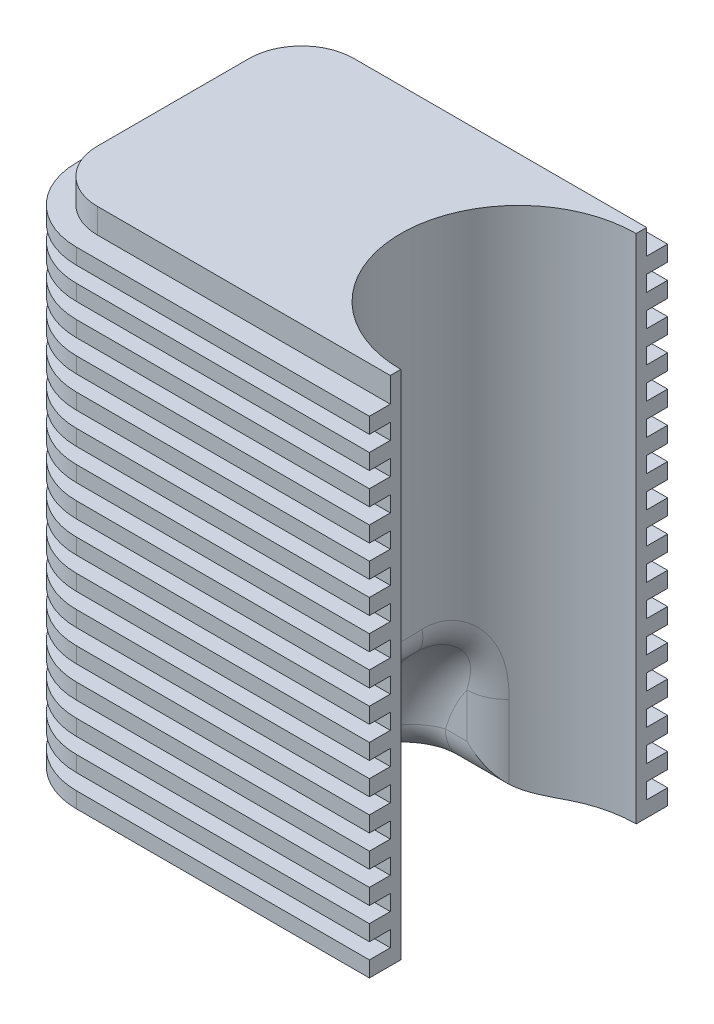
SolidWorks part; units mm, degrees
ref_plane "Ön Düzlem" through (0, 0, 0) normal (0, 0, 1) x (1, 0, 0)
ref_plane "Üst Düzlem" through (0, 0, 0) normal (0, 1, 0) x (1, 0, 0)
ref_plane "Sağ Düzlem" through (0, 0, 0) normal (1, 0, 0) x (0, 0, -1)
sketch "Sketch1" plane through (0, 0, 0) normal (0, 0, 1) x (1, 0, 0)
  line L0 (-32.985, 38.875) -> (-32.985, 48.875)
  line L1 (-22.985, 48.875) -> (32.985, 48.875)
  line L2 (-32.985, 38.875) -> (-32.985, -48.875)
  line L3 (-32.985, -48.875) -> (32.985, -48.875)
  line L4 (32.985, 48.875) -> (32.985, -48.875)
  line L5 (-32.985, 48.875) -> (32.985, -48.875) construction
  line L6 (-32.985, -48.875) -> (32.985, 48.875) construction
  line L7 (-32.985, 48.875) -> (-22.985, 48.875)
  point P0 (0, 0)
  dimension "D1" = 65.97
  dimension "D2" = 97.75
extrude "Boss-Extrude1" add sketch "Sketch1" along normal mid plane 49
sketch "Sketch2" plane through (0, 48.875, 0) normal (0, 1, 0) x (1, 0, 0)
  line L0 (32.985, -24.5) -> (32.985, 24.5) construction
  circle A0 centre (32.985, 0) radius 22.5
  dimension "D1" = 45
extrude "Cut-Extrude1" cut sketch "Sketch2" against normal up to surface (97.75 mm away) up to face at (0, -48.875, 0)
sketch "Sketch3" plane through (0, 0, 0) normal (0, 0, 1) x (1, 0, 0)
  circle A0 centre (32.985, -48.875) radius 35
  dimension "D1" = 70
extrude "Cut-Extrude2" cut sketch "Sketch3" against normal mid plane 25
fillet "Fillet1" radius 7.5 8 edges at (14.2767, -34.0848, -12.5) (6.1309, -48.875, -12.5) (-2.015, -48.875, 0) (2.3273, -31.9899, 12.5) (10.4911, -22.0604, -0.5234) (2.3273, -31.9899, -12.5) (6.1309, -48.875, 12.5) (14.2767, -34.0848, 12.5)
fillet "Fillet3" radius 10 2 edges at (-32.985, 0, -24.5) (-32.985, 0, 24.5)
sketch "Sketch7" plane through (0, -48.875, 0) normal (0, -1, 0) x (1, 0, 0)
  line L0 (32.985, 28.5) -> (-22.985, 28.5)
  line L1 (-36.985, 14.5) -> (-36.985, -14.5)
  line L2 (-22.985, -28.5) -> (32.985, -28.5)
  line L3 (32.985, 28.5) -> (32.985, 24.5)
  line L4 (32.985, -28.5) -> (32.985, -24.5)
  line L8 (-32.985, 14.5) -> (-32.985, -14.5)
  line L9 (-22.985, -24.5) -> (32.985, -24.5)
  line L10 (32.985, -24.5) -> (32.985, -22.5)
  line L11 (22.6772, -20) -> (6.5275, -20)
  line L12 (-8.848, -5) -> (-8.848, 5)
  line L13 (6.5275, 20) -> (22.6772, 20)
  line L14 (32.985, 22.5) -> (32.985, 24.5)
  line L15 (32.985, 24.5) -> (-22.985, 24.5)
  line L16 (-32.985, 14.5) -> (-32.985, -14.5)
  line L17 (-22.985, -24.5) -> (32.985, -24.5)
  line L18 (32.985, -24.5) -> (32.985, -22.5)
  line L22 (32.985, 22.5) -> (32.985, 24.5)
  line L23 (32.985, 24.5) -> (-22.985, 24.5)
  arc A0 (-22.985, 28.5) -> (-36.985, 14.5) centre (-22.985, 14.5) ccw
  arc A1 (-36.985, -14.5) -> (-22.985, -28.5) centre (-22.985, -14.5) ccw
  arc A4 (-32.985, -14.5) -> (-22.985, -24.5) centre (-22.985, -14.5) ccw
  arc A5 (22.6772, -20) -> (32.985, -22.5) centre (32.985, 0) ccw
  arc A6 (32.985, 22.5) -> (22.6772, 20) centre (32.985, 0) ccw
  arc A7 (-22.985, 24.5) -> (-32.985, 14.5) centre (-22.985, 14.5) ccw
  arc A8 (-32.985, -14.5) -> (-22.985, -24.5) centre (-22.985, -14.5) ccw
  arc A11 (-22.985, 24.5) -> (-32.985, 14.5) centre (-22.985, 14.5) ccw
  spline S2 degree 3 poles (320.5988, 929.3983) (147.1047, 209.6077) (54.4476, -29.3078) (3.0778, -19.6329) (2.5954, -19.5185) (1.6385, -19.2426) (1.1617, -19.0801) (-0.2292, -18.5296) (-1.1097, -18.0786) (-2.3606, -17.2767) (-2.7659, -16.9884) (-3.552, -16.3679) (-3.9294, -16.0382) (-5.0015, -15.0044) (-5.6426, -14.2512) (-6.4921, -13.0238) (-6.7578, -12.5957) (-7.2406, -11.7219) (-7.4584, -11.2759) (-8.0429, -9.9107) (-8.3412, -8.9649) (-19.9708, 47.4584) (290.1679, 138.7175) (991.1415, -8.1364) knots -6.415531 -6.415531 -6.415531 -6.415531 0.125 0.125 0.1875 0.1875 0.25 0.25 0.375 0.375 0.4375 0.4375 0.5 0.5 0.625 0.625 0.6875 0.6875 0.75 0.75 0.875 0.875 7.923707 7.923707 7.923707 7.923707 only from (6.5275, -20) to (-8.848, -5)
  spline S3 degree 3 poles (946.3703, -290.8944) (171.131, -113.2774) (-17.4982, -35.7953) (-8.4491, 8.4449) (-8.3255, 8.9256) (-8.0281, 9.8786) (-7.854, 10.3509) (-7.2679, 11.7231) (-6.7901, 12.5897) (-5.9438, 13.8176) (-5.6381, 14.217) (-4.9918, 14.9787) (-4.6519, 15.3409) (-3.5834, 16.373) (-2.8066, 16.989) (-1.1206, 18.0735) (-0.2353, 18.5262) (1.145, 19.074) (1.6142, 19.2348) (2.5714, 19.5124) (3.0609, 19.6293) (69.7275, 32.2412) (186.0404, -379.5955) (318.7265, -930.0151) knots -5.514491 -5.514491 -5.514491 -5.514491 0.125 0.125 0.1875 0.1875 0.25 0.25 0.375 0.375 0.4375 0.4375 0.5 0.5 0.625 0.625 0.75 0.75 0.8125 0.8125 0.875 0.875 9.306834 9.306834 9.306834 9.306834 only from (-8.848, 5) to (6.5275, 20)
  line M15 (-32.985, 14.5) -> (-32.985, -14.5)
  arc M16 (-32.985, -14.5) -> (-22.985, -24.5) centre (-22.985, -14.5) ccw
  line M17 (-22.985, -24.5) -> (32.985, -24.5)
  line M27 (32.985, 24.5) -> (-22.985, 24.5)
  arc M28 (-22.985, 24.5) -> (-32.985, 14.5) centre (-22.985, 14.5) ccw
  dimension "D3" = 14
  dimension "D1" = 0
  dimension "D2" = 4
extrude "Boss-Extrude2" add sketch "Sketch7" against normal blind 3 contours L1 A1 L2 L4 L3 L0 A0 M17 M16 M15 M28 M27 region at (32.0825, -48.875, 26.5) region at (25.5628, -48.875, -26.3573)
pattern_linear "LPattern1" count 16 spacing 6 along (0, 1, 0) of "Boss-Extrude2"
